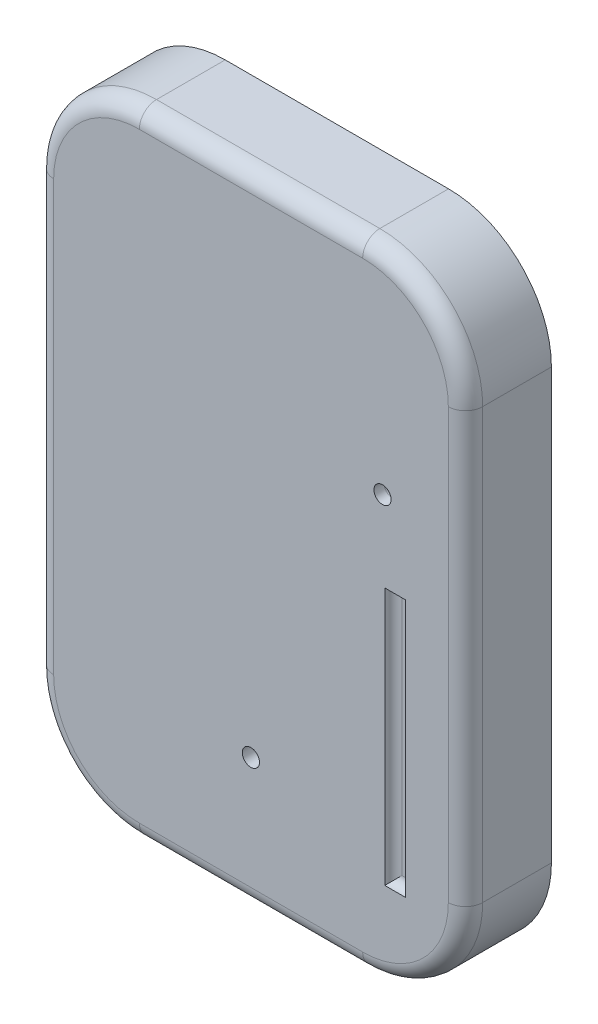
SolidWorks part; units mm, degrees
ref_plane "Front Plane" through (0, 0, 0) normal (0, 0, 1) x (1, 0, 0)
ref_plane "Top Plane" through (0, 0, 0) normal (0, 1, 0) x (1, 0, 0)
ref_plane "Right Plane" through (0, 0, 0) normal (1, 0, 0) x (0, 0, -1)
ref_plane "Plane1" through (0, 0, 26.2227) normal (0, 0, 1) x (1, 0, 0)
sketch "Sketch1" plane through (0, 0, 26.2227) normal (0, 0, 1) x (1, 0, 0)
  line L0 (18.3237, 30.4008) -> (18.3237, 30.1008) construction
  line L1 (18.3237, 30.4008) -> (18.3237, 30.1008)
  line L2 (18.3237, 30.1008) -> (16.5072, 30.1008) construction
  line L3 (18.3237, 30.1008) -> (16.5072, 30.1008)
  line L4 (-5.1509, 30.4008) -> (-5.1509, 5.4007)
  line L5 (0.8364, -0.5866) -> (13.8364, -0.5866)
  line L6 (19.8237, 5.4007) -> (19.8237, 30.4008)
  line L7 (13.8364, 36.3881) -> (0.8364, 36.3881)
  line L8 (-5.1509, 30.4008) -> (-5.1509, 5.4007)
  line L9 (0.8364, -0.5866) -> (13.8364, -0.5866)
  line L10 (19.8237, 5.4007) -> (19.8237, 30.4008)
  line L11 (13.8364, 36.3881) -> (0.8364, 36.3881)
  line L12 (-3.8509, 29.4007) -> (-4.4509, 29.4007) construction
  line L13 (-3.6509, 29.4007) -> (-3.8509, 29.4007) construction
  line L14 (-3.6509, 29.4007) -> (-1.8106, 29.4007) construction
  line L15 (-1.8106, 29.4007) -> (-1.8106, 30.1008) construction
  line L16 (-1.8106, 30.1008) -> (-3.6509, 30.1008) construction
  line L17 (-3.6509, 30.1008) -> (-3.6509, 30.4008) construction
  line L18 (-4.4509, 29.4007) -> (-4.4509, 5.4007) construction
  line L19 (-4.4509, 5.4007) -> (-3.8509, 5.4007) construction
  line L20 (-3.8509, 5.4007) -> (-3.6509, 5.4007) construction
  line L21 (12.2966, 0.9134) -> (0.8364, 0.9134) construction
  line L22 (12.2966, 2.7448) -> (12.2966, 0.9134) construction
  line L23 (12.9966, 2.7448) -> (12.2966, 2.7448) construction
  line L24 (12.9966, 0.9134) -> (12.9966, 2.7448) construction
  line L25 (13.8364, 0.9134) -> (12.9966, 0.9134) construction
  line L26 (18.3237, 5.4007) -> (18.5237, 5.4007) construction
  line L27 (18.5237, 5.4007) -> (19.1237, 5.4007) construction
  line L28 (0.8364, 34.8881) -> (13.8364, 34.8881) construction
  line L29 (19.1237, 29.4007) -> (19.1237, 5.4007) construction
  line L30 (19.1237, 29.4007) -> (18.5237, 29.4007) construction
  line L31 (18.5237, 29.4007) -> (18.3237, 29.4007) construction
  line L32 (16.5072, 29.4007) -> (18.3237, 29.4007) construction
  line L33 (16.5072, 30.1008) -> (16.5072, 29.4007) construction
  line L34 (-3.8509, 29.4007) -> (-4.4509, 29.4007)
  line L35 (-3.6509, 29.4007) -> (-3.8509, 29.4007)
  line L36 (-3.6509, 29.4007) -> (-1.8106, 29.4007)
  line L37 (-1.8106, 29.4007) -> (-1.8106, 30.1008)
  line L38 (-1.8106, 30.1008) -> (-3.6509, 30.1008)
  line L39 (-3.6509, 30.1008) -> (-3.6509, 30.4008)
  line L40 (-4.4509, 29.4007) -> (-4.4509, 5.4007)
  line L41 (-4.4509, 5.4007) -> (-3.8509, 5.4007)
  line L42 (-3.8509, 5.4007) -> (-3.6509, 5.4007)
  line L43 (12.2966, 0.9134) -> (0.8364, 0.9134)
  line L44 (12.2966, 2.7448) -> (12.2966, 0.9134)
  line L45 (12.9966, 2.7448) -> (12.2966, 2.7448)
  line L46 (12.9966, 0.9134) -> (12.9966, 2.7448)
  line L47 (13.8364, 0.9134) -> (12.9966, 0.9134)
  line L48 (18.3237, 5.4007) -> (18.5237, 5.4007)
  line L49 (18.5237, 5.4007) -> (19.1237, 5.4007)
  line L50 (0.8364, 34.8881) -> (13.8364, 34.8881)
  line L51 (19.1237, 29.4007) -> (19.1237, 5.4007)
  line L52 (19.1237, 29.4007) -> (18.5237, 29.4007)
  line L53 (18.5237, 29.4007) -> (18.3237, 29.4007)
  line L54 (16.5072, 29.4007) -> (18.3237, 29.4007)
  line L55 (16.5072, 30.1008) -> (16.5072, 29.4007)
  arc A0 (0.8364, 34.8881) -> (-3.6509, 30.4008) centre (0.8364, 30.4008) ccw construction
  arc A1 (0.8364, 34.8881) -> (-3.6509, 30.4008) centre (0.8364, 30.4008) ccw
  arc A2 (18.3237, 30.4008) -> (13.8364, 34.8881) centre (13.8364, 30.4008) ccw construction
  arc A3 (18.3237, 30.4008) -> (13.8364, 34.8881) centre (13.8364, 30.4008) ccw
  arc A4 (0.8364, 36.3881) -> (-5.1509, 30.4008) centre (0.8364, 30.4008) ccw
  arc A5 (-5.1509, 5.4007) -> (0.8364, -0.5866) centre (0.8364, 5.4007) ccw
  arc A6 (13.8364, -0.5866) -> (19.8237, 5.4007) centre (13.8364, 5.4007) ccw
  arc A7 (19.8237, 30.4008) -> (13.8364, 36.3881) centre (13.8364, 30.4008) ccw
  arc A8 (0.8364, 36.3881) -> (-5.1509, 30.4008) centre (0.8364, 30.4008) ccw
  arc A9 (-5.1509, 5.4007) -> (0.8364, -0.5866) centre (0.8364, 5.4007) ccw
  arc A10 (13.8364, -0.5866) -> (19.8237, 5.4007) centre (13.8364, 5.4007) ccw
  arc A11 (19.8237, 30.4008) -> (13.8364, 36.3881) centre (13.8364, 30.4008) ccw
  arc A12 (-3.6509, 5.4007) -> (0.8364, 0.9134) centre (0.8364, 5.4007) ccw construction
  arc A13 (13.8364, 0.9134) -> (18.3237, 5.4007) centre (13.8364, 5.4007) ccw construction
  arc A14 (-3.6509, 5.4007) -> (0.8364, 0.9134) centre (0.8364, 5.4007) ccw
  arc A15 (13.8364, 0.9134) -> (18.3237, 5.4007) centre (13.8364, 5.4007) ccw
  dimension "D1" = 0
extrude "Boss-Extrude1" add sketch "Sketch1" along normal blind 4
sketch "Sketch2" plane through (0, 0, 30.2227) normal (0, 0, 1) x (1, 0, 0)
  line L4 (-5.1509, 30.4008) -> (-5.1509, 5.4007)
  line L5 (0.8364, -0.5866) -> (13.8364, -0.5866)
  line L6 (19.8237, 5.4007) -> (19.8237, 30.4008)
  line L7 (13.8364, 36.3881) -> (0.8364, 36.3881)
  line L8 (-5.1509, 30.4008) -> (-5.1509, 5.4007)
  line L9 (0.8364, -0.5866) -> (13.8364, -0.5866)
  line L10 (19.8237, 5.4007) -> (19.8237, 30.4008)
  line L11 (13.8364, 36.3881) -> (0.8364, 36.3881)
  arc A4 (0.8364, 36.3881) -> (-5.1509, 30.4008) centre (0.8364, 30.4008) ccw
  arc A5 (-5.1509, 5.4007) -> (0.8364, -0.5866) centre (0.8364, 5.4007) ccw
  arc A6 (13.8364, -0.5866) -> (19.8237, 5.4007) centre (13.8364, 5.4007) ccw
  arc A7 (19.8237, 30.4008) -> (13.8364, 36.3881) centre (13.8364, 30.4008) ccw
  arc A8 (0.8364, 36.3881) -> (-5.1509, 30.4008) centre (0.8364, 30.4008) ccw
  arc A9 (-5.1509, 5.4007) -> (0.8364, -0.5866) centre (0.8364, 5.4007) ccw
  arc A10 (13.8364, -0.5866) -> (19.8237, 5.4007) centre (13.8364, 5.4007) ccw
  arc A11 (19.8237, 30.4008) -> (13.8364, 36.3881) centre (13.8364, 30.4008) ccw
  dimension "D1" = 0
extrude "Boss-Extrude2" add sketch "Sketch2" along normal blind 1
ref_plane "Plane2" through (0, 20, 0) normal (0, 1, 0) x (1, 0, 0)
sketch "Sketch4" plane through (0, 20, 0) normal (0, 1, 0) x (1, 0, 0)
  line L0 (-4.4509, -26.2227) -> (-4.1509, -27.2227)
  line L1 (-4.4509, -27.2227) -> (-4.0509, -27.2227) construction
  line L2 (-4.1509, -27.2227) -> (-4.4509, -27.2227)
  line L3 (-4.4509, -27.2227) -> (-4.4509, -26.2227)
  line L4 (19.1237, -26.2227) -> (18.8237, -27.2227)
  line L5 (18.7237, -27.2227) -> (19.1237, -27.2227) construction
  line L6 (18.8237, -27.2227) -> (19.1237, -27.2227)
  line L7 (19.1237, -27.2227) -> (19.1237, -26.2227)
  dimension "D1" = 0.3
  dimension "D2" = 0.3
extrude "Boss-Extrude3" add sketch "Sketch4" along normal up to surface and the other way up to surface up to face at (-3.1308, 29.4007, 28.2227) other way up to face at (-4.0509, 5.4007, 28.2227)
fillet "Fillet1" radius 1 8 edges at (7.3364, 36.3881, 31.2227) (18.0701, 34.6344, 31.2227) (19.8237, 17.9007, 31.2227) (18.0701, 1.167, 31.2227) (7.3364, -0.5866, 31.2227) (-3.3973, 1.167, 31.2227) (-5.1509, 17.9007, 31.2227) (-3.3973, 34.6344, 31.2227)
sketch "Sketch5" plane through (0, 0, 31.2227) normal (0, 0, 1) x (1, 0, 0)
  line L0 (7.3287, 6.9749) -> (7.3287, 6.9639) construction
  circle A0 centre (7.3287, 6.9694) radius 0.5
  circle A1 centre (14.9927, 24.0476) radius 0.5
  dimension "D1" = 1
  dimension "D2" = 1
extrude "Cut-Extrude1" cut sketch "Sketch5" against normal up to next
sketch "Sketch6" plane through (0, 0, 31.2227) normal (0, 0, 1) x (1, 0, 0)
  line L0 (13.8364, -0.5866) -> (0.8364, -0.5866) construction
  line L1 (15.1237, 19.4134) -> (16.3237, 19.4134)
  line L2 (15.1237, 19.4134) -> (15.1237, 4.4134)
  line L3 (15.1237, 4.4134) -> (16.3237, 4.4134)
  line L4 (16.3237, 19.4134) -> (16.3237, 4.4134)
  line L5 (19.8237, 30.4008) -> (19.8237, 5.4007) construction
  dimension "D1" = 1.2
  dimension "D2" = 15
  dimension "D3" = 5
  dimension "D4" = 3.5
extrude "Cut-Extrude2" cut sketch "Sketch6" against normal blind 0.5
fillet "Fillet2" radius 0.5 4 edges at (15.7237, 19.4134, 30.7227) (16.3237, 11.9134, 30.7227) (15.7237, 4.4134, 30.7227) (15.1237, 11.9134, 30.7227)
sketch "Sketch7" plane through (0, 0, 30.2227) normal (0, 0, -1) x (-1, 0, 0)
  line L0 (-7.3287, 6.9749) -> (-7.3287, 6.9639) construction
  circle A0 centre (-7.3287, 6.9694) radius 0.5
  circle A1 centre (-7.3287, 6.9694) radius 0.9
  dimension "D1" = 0.4
extrude "Boss-Extrude4" add sketch "Sketch7" along normal blind 2
fillet "Fillet3" radius 0.4 1 edges at (8.2287, 6.9694, 30.2227)
sketch "Sketch8" plane through (0, 0, 30.2227) normal (0, 0, -1) x (-1, 0, 0)
  line L0 (-16.2072, 30.4008) -> (-16.2072, 29.1007) construction
  line L1 (-14.2072, 30.1008) -> (-0.4894, 30.1008)
  line L2 (-14.2072, 30.1008) -> (-14.2072, 28.7008)
  line L3 (-14.2072, 28.7008) -> (-0.4894, 28.7008)
  line L4 (-0.4894, 30.1008) -> (-0.4894, 28.7008)
  line L5 (1.5106, 29.1007) -> (1.5106, 30.4008) construction
  line L6 (-16.5072, 30.1008) -> (-18.3237, 30.1008) construction
  dimension "D1" = 2
  dimension "D2" = 2
  dimension "D3" = 1.4
extrude "Boss-Extrude5" add sketch "Sketch8" along normal up to surface (2.5999 mm away)
fillet "Fillet4" radius 0.4 25 edges at (14.2072, 29.4008, 30.2227) (7.3483, 28.7008, 30.2227) (7.3483, 30.1008, 30.2227) (0.4894, 29.4008, 30.2227) (-2.7308, 30.1008, 30.2227) (-1.8106, 29.7507, 30.2227) (-3.1308, 29.4007, 30.2227) (-4.4509, 17.4007, 30.2227) (-4.0509, 5.4007, 30.2227) (-2.3366, 2.2277, 30.2227) (6.5665, 0.9134, 30.2227) (12.2966, 1.8291, 30.2227) (12.6466, 2.7448, 30.2227) (12.9966, 1.8291, 30.2227) (13.4165, 0.9134, 30.2227) (17.0094, 2.2277, 30.2227) (18.7237, 5.4007, 30.2227) (19.1237, 17.4007, 30.2227) (17.8155, 29.4007, 30.2227) (16.5072, 29.7507, 30.2227) (17.4155, 30.1008, 30.2227) (17.0094, 33.5738, 30.2227) (7.3364, 34.8881, 30.2227) (-2.3366, 33.5738, 30.2227) (15.4927, 24.0476, 30.2227)
